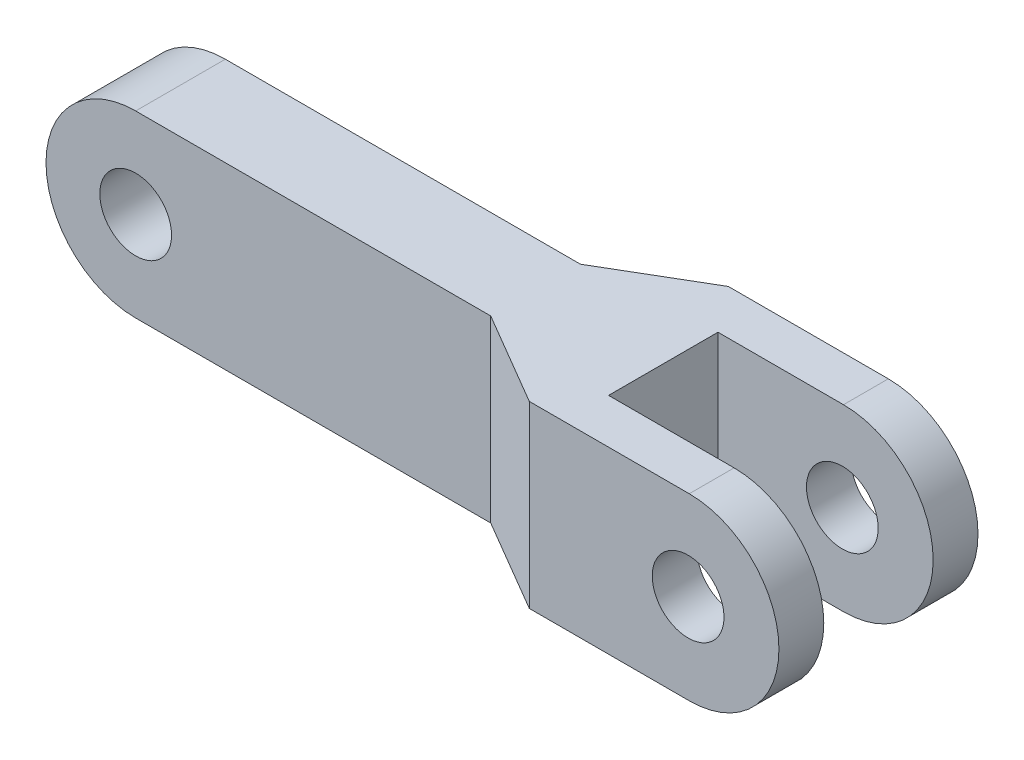
SolidWorks part; units mm, degrees
ref_plane "Plan de face" through (0, 0, 0) normal (0, 0, 1) x (1, 0, 0)
ref_plane "Plan de dessus" through (0, 0, 0) normal (0, 1, 0) x (1, 0, 0)
ref_plane "Plan de droite" through (0, 0, 0) normal (1, 0, 0) x (0, 0, -1)
sketch "Esquisse1" plane through (0, 0, 0) normal (0, 0, 1) x (1, 0, 0)
  line L0 (-15, 0) -> (10, 0) construction
  line L1 (-15, 5) -> (10, 5)
  line L2 (-15, -5) -> (10, -5)
  line L3 (10, 5) -> (10, -5)
  arc A0 (-15, 5) -> (-15, -5) centre (-15, 0) ccw
  circle A2 centre (-15, 0) radius 2
  point P2 (0, 0)
  dimension "D2" = 5
  dimension "D3" = 4
  dimension "D1" = 25
extrude "Boss.-Extru.1" add sketch "Esquisse1" along normal blind 5
sketch "Esquisse2" plane through (0, 5, 0) normal (0, 1, 0) x (1, 0, 0)
  line L0 (10, -2.5) -> (26.9846, -2.5) construction
  line L1 (10, -5) -> (10, 0) construction
  line L2 (11.9207, 0.55) -> (23.9207, 0.55)
  line L3 (11.9207, 0.55) -> (11.9207, 3.05)
  line L4 (11.9207, 3.05) -> (23.9207, 3.05)
  line L5 (23.9207, 0.55) -> (23.9207, 3.05)
  line L6 (10, 0) -> (-15, 0) construction
  line L7 (10, 0) -> (-15, 0)
  line L8 (11.9207, -5.55) -> (23.9207, -5.55)
  line L9 (11.9207, -5.55) -> (11.9207, -8.05)
  line L10 (11.9207, -8.05) -> (23.9207, -8.05)
  line L11 (23.9207, -5.55) -> (23.9207, -8.05)
  dimension "D1" = 12
  dimension "D2" = 2.5
  dimension "D3" = 3.05
extrude "Boss.-Extru.2" add sketch "Esquisse2" against normal through all separate body contours L2 L5 L4 L3 | L11 L8 L9 L10 region at (17.9207, 5, -1.8) region at (17.9207, 5, 6.8)
sketch "Esquisse5" plane through (0, 0, -0.55) normal (0, 0, 1) x (1, 0, 0)
  line L0 (10, -5) -> (10, 5) construction
  line L1 (10, -5) -> (10, 5)
  line L2 (11.9207, -5) -> (11.9207, 5) construction
  line L3 (11.9207, -5) -> (11.9207, 5)
  line L4 (11.9207, 5) -> (23.9207, 5) construction
  line L5 (11.9207, 5) -> (10, 5)
  line L6 (11.9207, -5) -> (23.9207, -5) construction
  line L7 (11.9207, -5) -> (10, -5)
  line L8 (10, -5) -> (11.9207, -5)
extrude "Boss.-Extru.4" add sketch "Esquisse5" along normal up to surface (6.1 mm away) contours L3 L5 L1 L7 up to face at (17.9207, 0, 5.55)
sketch "Esquisse7" plane through (11.9207, 0, 0) normal (-1, 0, 0) x (0, 0, 1)
  line L4 (-0.55, 5) -> (-3.05, 5)
  line L5 (-3.05, 5) -> (-3.05, -5)
  line L6 (-3.05, -5) -> (-0.55, -5)
  line L7 (-0.55, -5) -> (-0.55, 5)
  line L8 (-0.55, 5) -> (-3.05, 5)
  line L9 (-3.05, 5) -> (-3.05, -5)
  line L10 (-3.05, -5) -> (-0.55, -5)
  line L11 (-0.55, -5) -> (-0.55, 5)
  line L12 (8.05, 5) -> (5.55, 5)
  line L13 (5.55, 5) -> (5.55, -5)
  line L14 (5.55, -5) -> (8.05, -5)
  line L15 (8.05, -5) -> (8.05, 5)
  line L16 (8.05, 5) -> (5.55, 5)
  line L17 (5.55, 5) -> (5.55, -5)
  line L18 (5.55, -5) -> (8.05, -5)
  line L19 (8.05, -5) -> (8.05, 5)
  dimension "D1" = 0
  dimension "D2" = 0
extrude "Boss.-Extru.6" add sketch "Esquisse7" along normal up to surface (1.9207 mm away) up to face at (10, 0, -0.275)
fillet "Congé4" 2 edges at (23.9207, -5, 6.8) (23.9207, 5, 6.8) type full round first side face at (10.7937, -5, 2.5) second side face at (10.7937, 5, 2.5) middle face at (23.9207, 0, 6.8)
sketch "Esquisse4" plane through (0, 0, -3.05) normal (0, 0, -1) x (-1, 0, 0)
  circle A2 centre (-18.8561, 0) radius 2
  dimension "D1" = 4
sketch "Esquisse6" plane through (0, 5, 0) normal (0, 1, 0) x (1, 0, 0)
  line L0 (10, 3.05) -> (4.799, 0)
  line L1 (10, 0) -> (-15, 0) construction
  line L2 (4.799, 0) -> (10, 0)
  line L3 (10, 0) -> (10, 3.05)
  line L4 (5.2067, -2.5) -> (23.095, -2.5) construction
  line L5 (10, -8.05) -> (4.799, -5)
  line L6 (4.799, -5) -> (10, -5)
  line L7 (10, -5) -> (10, -8.05)
  line L8 (10, 0) -> (10, 3.05) construction
  line L9 (10, 3.05) -> (23.9207, 3.05) construction
  line M13 (10, 0) -> (-15, 0)
  line M15 (-15, -5) -> (10, -5)
extrude "Boss.-Extru.5" add sketch "Esquisse6" against normal through all contours L0 M13 | L5 M15 region at (8.2663, 5, -1.0167) region at (8.2663, 5, 6.0167)
extrude "Enlèv. mat.-Extru.2" cut sketch "Esquisse4" against normal through all
fillet "Congé5" 2 edges at (23.9207, 5, -1.8) (23.9207, -5, -1.8) type full round first side face at (9.0935, 5, 2.5) second side face at (9.0935, -5, 2.5) middle face at (23.9207, 0, -1.8)
